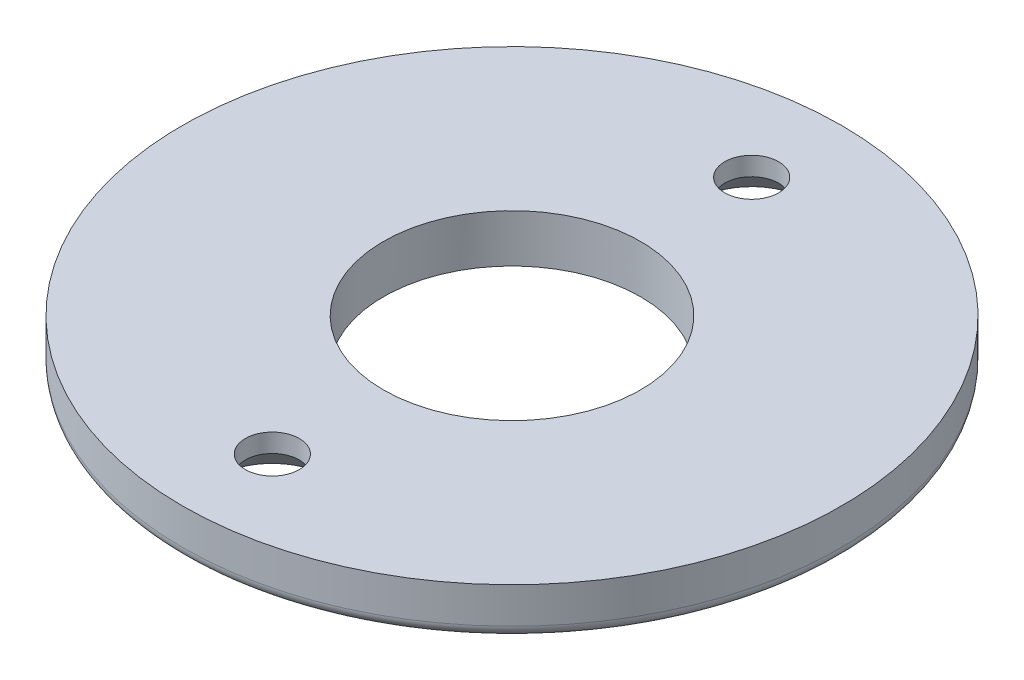
SolidWorks part; units mm, degrees
note: '?' marks a value the reader was unsure of.
ref_plane "Front Plane" through (0, 0, 0) normal (0, 0, 1) x (1, 0, 0)
ref_plane "Top Plane" through (0, 0, 0) normal (0, 1, 0) x (1, 0, 0)
ref_plane "Right Plane" through (0, 0, 0) normal (1, 0, 0) x (0, 0, -1)
ref_axis "X" through (88.99, 0, 0) along (-1, 0, 0)?
ref_axis "Y" through (0, 55, 0) along (0, -1, 0)?
ref_axis "Z" through (0, 0, -88.99) along (0, 0, 1)?
sketch "Sketch1" plane through (0, 0, 0) normal (0, 0, 1) x (1, 0, 0)
  line L0 (0, 0) -> (0, -21.8723) construction
  line L4 (-27.5, 0) -> (-27.5, 4)
  line L5 (-27.5, 4) -> (-13, 4)
  line L7 (-11, 3) -> (0, 3)
  line L8 (0, 3) -> (0, 0)
  line L9 (0, 0) -> (-27.5, 0)
  line L10 (-13, 4) -> (-13, 8)
  line L11 (-13, 8) -> (-11, 8)
  line L12 (-11, 8) -> (-11, 3)
  dimension "D1" = 55
  dimension "D2" = 2
  dimension "D3" = 4
  dimension "D4" = 3
  dimension "D5" = 13
  dimension "D6" = 4
revolve "Revolve1" add sketch "Sketch1" angle 360 about L0
hole_wizard "CSK SLOT for M4 Countersunk Flat Head Screw1" positions "Sketch2" profile "Sketch3" size "M4" standard "DIN" slot yes end condition up to next
sketch "Sketch2" plane through (0, 0, 0) normal (0, 1, 0) x (1, 0, 0)
  circle A0 centre (0, 0) radius 20
  point P5 (0, 20)
  point P9 (0, -20)
  dimension "D1" = 40
sketch "Sketch3" plane through (0, 0, 20) normal (1, 0, 0) x (0, 0, -1)
  line L0 (0, 0) -> (0, 4)
  line L1 (0, 4) -> (2.25, 4)
  line L2 (2.25, 4) -> (2.25, 2.45)
  line L3 (2.25, 2.45) -> (4.7, 0)
  line L5 (4.7, 0) -> (0, 0)
  line L6 (-2.25, 2.45) -> (-4.7, 0) construction
  line L11 (0, -6.35) -> (0, 107.95) construction
  dimension "Thru Hole Dia." = 4.5
  dimension "Thru Hole Depth" = 4
  dimension "Near C'Sink Dia." = 9.4
  dimension "Near C'Sink Angle" = 90
sketch "Sketch4" plane through (0, 3, 0) normal (0, 1, 0) x (1, 0, 0)
  circle A0 centre (0, 0) radius 7
  dimension "D1" = 14
extrude "Cut-Extrude1" [suppressed] cut sketch "Sketch4" against normal through all
fillet "Fillet1" radius 2 1 edges at (0, 3, 11)
fillet "Fillet2" radius 1 1 edges at (0, 0, 27.5)
sketch "Sketch5" plane through (0, 4, 0) normal (0, 1, 0) x (1, 0, 0)
  circle A0 centre (0, 0) radius 32.9408
extrude "Cut-Extrude2" cut sketch "Sketch5" along normal blind 10
sketch "Sketch6" plane through (0, 4, 0) normal (0, 1, 0) x (1, 0, 0)
  circle A0 centre (0, 0) radius 10.7321
extrude "Cut-Extrude3" cut sketch "Sketch6" against normal blind 10
